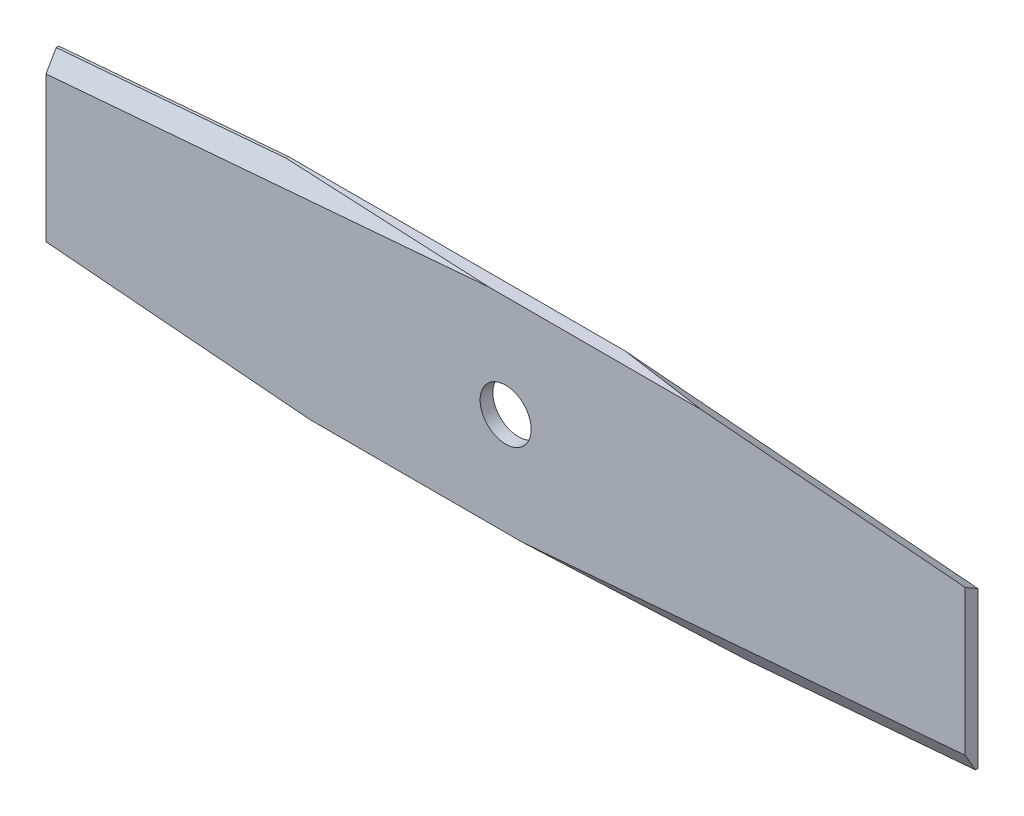
SolidWorks part; units mm, degrees
material "Cast Alloy Steel"
ref_plane "Front Plane" through (0, 0, 0) normal (0, 0, 1) x (1, 0, 0)
ref_plane "Top Plane" through (0, 0, 0) normal (0, 1, 0) x (1, 0, 0)
ref_plane "Right Plane" through (0, 0, 0) normal (1, 0, 0) x (0, 0, -1)
ref_axis "Blade rotation axis" through (0, 0, 100.1175) along (0, 0, 1)
sketch "Sketch1" plane through (0, 0, 0) normal (0, 0, 1) x (1, 0, 0)
  line L0 (-114.3, 0) -> (114.3, 0) construction
  line L1 (-57.15, 25.4) -> (57.15, 25.4)
  line L2 (57.15, -25.4) -> (-57.15, -25.4)
  line L3 (0, 25.4) -> (0, -25.4) construction
  line L4 (-57.15, 25.4) -> (-114.3, 20.6375)
  line L5 (-114.3, 20.6375) -> (-114.3, -20.6375)
  line L6 (-114.3, -20.6375) -> (-57.15, -25.4)
  line L7 (57.15, -25.4) -> (114.3, -20.6375)
  line L8 (114.3, -20.6375) -> (114.3, 20.6375)
  line L9 (114.3, 20.6375) -> (57.15, 25.4)
  dimension "D1" = 50.8
  dimension "D2" = 114.3
  dimension "D3" = 41.275
  dimension "D4" = 228.6
extrude "Boss-Extrude1" add sketch "Sketch1" along normal blind 3.175
sketch "Sketch2" plane through (0, 0, 3.175) normal (0, 0, 1) x (1, 0, 0)
  circle A0 centre (0, 0) radius 6.35
  dimension "D1" = 12.7
extrude "Cut-Extrude1" cut sketch "Sketch2" against normal through all
chamfer "Chamfer1" distance 2.54 angle 60 4 edges at (85.725, 23.0188, 0) (-85.725, -23.0188, 0) (-85.725, 23.0188, 3.175) (85.725, -23.0188, 3.175) first distance on face at (6.35, 0, 0) first distance on face at (-85.725, 23.0188, 1.5875) first distance on face at (85.725, -23.0188, 1.5875)
sketch "Sketch3" plane through (0, 0, 0) normal (0, 0, 1) x (1, 0, 0)
  circle A0 centre (0, 0) radius 116.1482
  dimension "D1" = 232.2963
